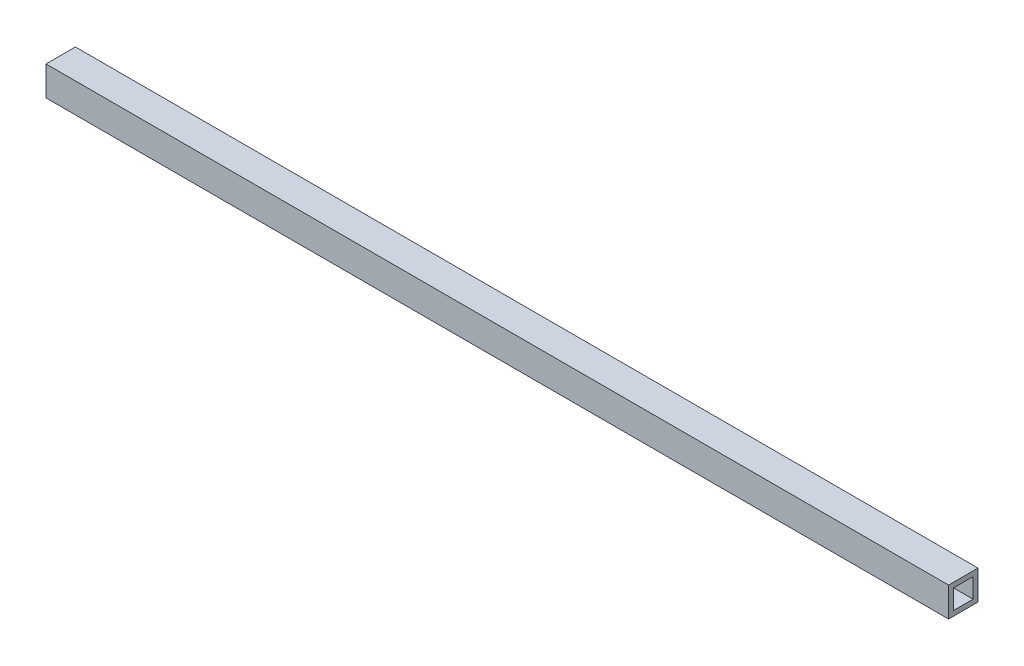
SolidWorks part; units mm, degrees
ref_plane "Front Plane" through (0, 0, 0) normal (0, 0, 1) x (1, 0, 0)
ref_plane "Top Plane" through (0, 0, 0) normal (0, 1, 0) x (1, 0, 0)
ref_plane "Right Plane" through (0, 0, 0) normal (1, 0, 0) x (0, 0, -1)
sketch "Sketch1" plane through (0, 0, 0) normal (1, 0, 0) x (0, 0, -1)
  line L1 (0, 0) -> (12.7, 0)
  line L2 (0, 0) -> (0, 12.7)
  line L3 (0, 12.7) -> (12.7, 12.7)
  line L4 (12.7, 0) -> (12.7, 12.7)
  dimension "D1" = 12.7
  dimension "D2" = 12.7
extrude "Extrude-Thin1" add sketch "Sketch1" along normal blind 584.2 thin thin type one direction wall 3.175
